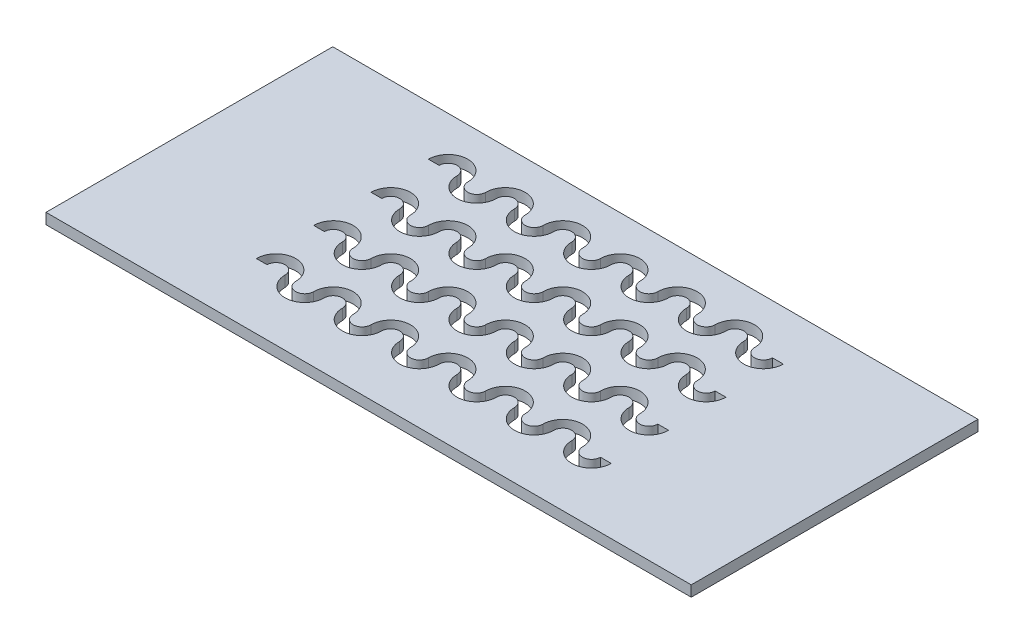
SolidWorks part; units mm, degrees
ref_plane "Front Plane" through (0, 0, 0) normal (0, 0, 1) x (1, 0, 0)
ref_plane "Top Plane" through (0, 0, 0) normal (0, 1, 0) x (1, 0, 0)
ref_plane "Right Plane" through (0, 0, 0) normal (1, 0, 0) x (0, 0, -1)
sketch "Sketch1" plane through (0, 0, 0) normal (0, 1, 0) x (1, 0, 0)
  line L1 (0, 0) -> (180, 0)
  line L2 (0, 0) -> (0, 80)
  line L3 (0, 80) -> (180, 80)
  line L4 (180, 0) -> (180, 80)
  arc A28 (50, 66.1743) -> (42, 66.1743) centre (46, 66.1743) ccw
  arc A29 (50, 66.1743) -> (58, 66.1743) centre (54, 66.1743) ccw
  arc A30 (66, 66.1743) -> (58, 66.1743) centre (62, 66.1743) ccw
  arc A31 (66, 66.1743) -> (74, 66.1743) centre (70, 66.1743) ccw
  arc A44 (50, 50.1743) -> (42, 50.1743) centre (46, 50.1743) ccw
  arc A45 (50, 50.1743) -> (58, 50.1743) centre (54, 50.1743) ccw
  arc A46 (66, 50.1743) -> (58, 50.1743) centre (62, 50.1743) ccw
  arc A47 (66, 50.1743) -> (74, 50.1743) centre (70, 50.1743) ccw
  arc A60 (50, 34.1743) -> (42, 34.1743) centre (46, 34.1743) ccw
  arc A61 (50, 34.1743) -> (58, 34.1743) centre (54, 34.1743) ccw
  arc A62 (66, 34.1743) -> (58, 34.1743) centre (62, 34.1743) ccw
  arc A63 (66, 34.1743) -> (74, 34.1743) centre (70, 34.1743) ccw
  arc A76 (50, 18.1743) -> (42, 18.1743) centre (46, 18.1743) ccw
  arc A77 (50, 18.1743) -> (58, 18.1743) centre (54, 18.1743) ccw
  arc A78 (66, 18.1743) -> (58, 18.1743) centre (62, 18.1743) ccw
  arc A79 (66, 18.1743) -> (74, 18.1743) centre (70, 18.1743) ccw
  arc A126 (82, 66.1743) -> (74, 66.1743) centre (78, 66.1743) ccw
  arc A127 (82, 66.1743) -> (90, 66.1743) centre (86, 66.1743) ccw
  arc A128 (98, 66.1743) -> (90, 66.1743) centre (94, 66.1743) ccw
  arc A129 (98, 66.1743) -> (106, 66.1743) centre (102, 66.1743) ccw
  arc A130 (114, 66.1743) -> (106, 66.1743) centre (110, 66.1743) ccw
  arc A131 (114, 66.1743) -> (122, 66.1743) centre (118, 66.1743) ccw
  arc A132 (130, 66.1743) -> (122, 66.1743) centre (126, 66.1743) ccw
  arc A133 (130, 66.1743) -> (138, 66.1743) centre (134, 66.1743) ccw
  arc A140 (82, 50.1743) -> (74, 50.1743) centre (78, 50.1743) ccw
  arc A141 (82, 50.1743) -> (90, 50.1743) centre (86, 50.1743) ccw
  arc A142 (98, 50.1743) -> (90, 50.1743) centre (94, 50.1743) ccw
  arc A143 (98, 50.1743) -> (106, 50.1743) centre (102, 50.1743) ccw
  arc A144 (114, 50.1743) -> (106, 50.1743) centre (110, 50.1743) ccw
  arc A145 (114, 50.1743) -> (122, 50.1743) centre (118, 50.1743) ccw
  arc A146 (130, 50.1743) -> (122, 50.1743) centre (126, 50.1743) ccw
  arc A147 (130, 50.1743) -> (138, 50.1743) centre (134, 50.1743) ccw
  arc A154 (82, 34.1743) -> (74, 34.1743) centre (78, 34.1743) ccw
  arc A155 (82, 34.1743) -> (90, 34.1743) centre (86, 34.1743) ccw
  arc A156 (98, 34.1743) -> (90, 34.1743) centre (94, 34.1743) ccw
  arc A157 (98, 34.1743) -> (106, 34.1743) centre (102, 34.1743) ccw
  arc A158 (114, 34.1743) -> (106, 34.1743) centre (110, 34.1743) ccw
  arc A159 (114, 34.1743) -> (122, 34.1743) centre (118, 34.1743) ccw
  arc A160 (130, 34.1743) -> (122, 34.1743) centre (126, 34.1743) ccw
  arc A161 (130, 34.1743) -> (138, 34.1743) centre (134, 34.1743) ccw
  arc A168 (82, 18.1743) -> (74, 18.1743) centre (78, 18.1743) ccw
  arc A169 (82, 18.1743) -> (90, 18.1743) centre (86, 18.1743) ccw
  arc A170 (98, 18.1743) -> (90, 18.1743) centre (94, 18.1743) ccw
  arc A171 (98, 18.1743) -> (106, 18.1743) centre (102, 18.1743) ccw
  arc A172 (114, 18.1743) -> (106, 18.1743) centre (110, 18.1743) ccw
  arc A173 (114, 18.1743) -> (122, 18.1743) centre (118, 18.1743) ccw
  arc A174 (130, 18.1743) -> (122, 18.1743) centre (126, 18.1743) ccw
  arc A175 (130, 18.1743) -> (138, 18.1743) centre (134, 18.1743) ccw
  point P5 (0, 0)
  dimension "D1" = 180
  dimension "D2" = 80
  dimension "D3" = 50
  dimension "D4" = 50
  dimension "D5" = 50
  dimension "D6" = 50
extrude "Boss-Extrude1" add sketch "Sketch1" along normal blind 3
extrude "Cut-Extrude-Thin1" cut sketch "Sketch1<3>" against normal mid plane 10 thin contours A133 A132 A131 A130 A129 A128 A127 A126 A31 A30 A29 A28 | A44 A45 A46 A47 A140 A141 A142 A143 A144 A145 A146 A147 | A161 A160 A159 A158 A157 A156 A155 A154 A63 A62 A61 A60 | A175 A174 A173 A172 A171 A170 A169 A168 A79 A78 A77 A76 thin type mid plane wall 3
sketch "Sketch1<3>" plane through (0, 0, 0) normal (0, 1, 0) x (1, 0, 0) same geometry as "Sketch1"
